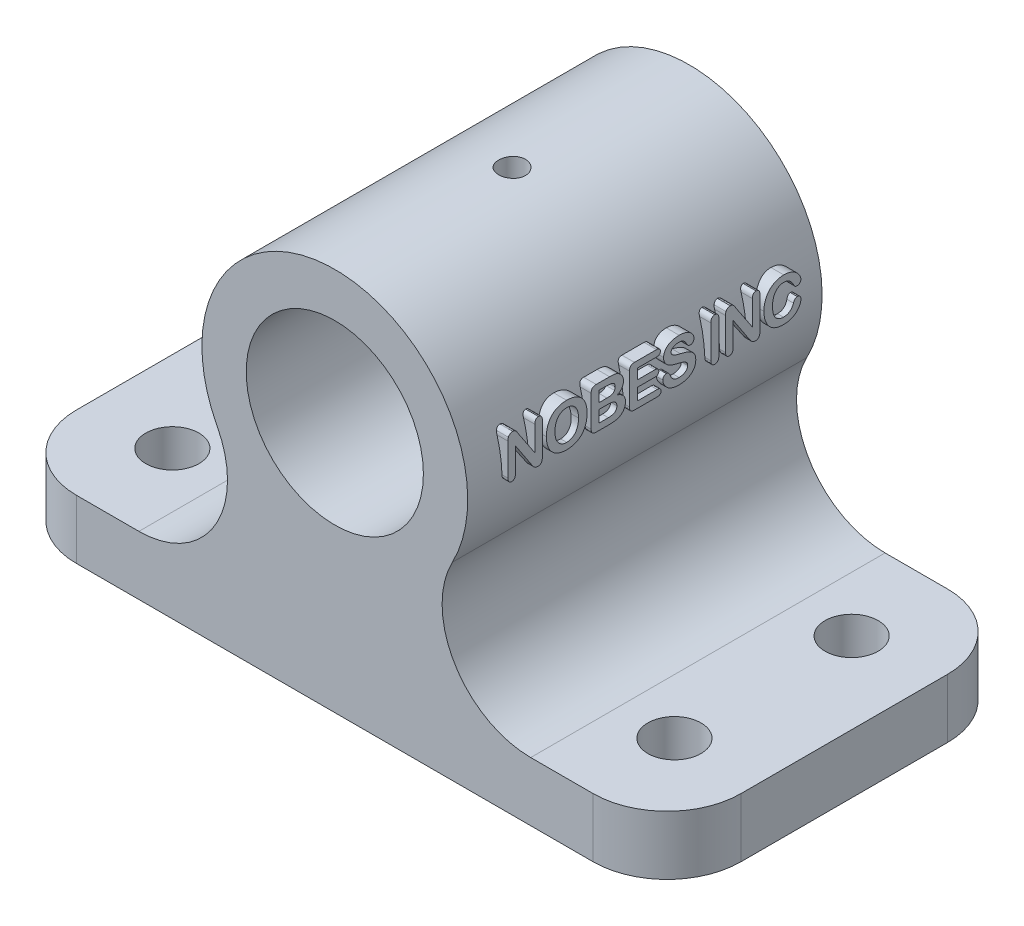
SolidWorks part; units mm, degrees
material "Malleable Cast Iron"
ref_plane "Front Plane" through (0, 0, 0) normal (0, 0, 1) x (1, 0, 0)
ref_plane "Top Plane" through (0, 0, 0) normal (0, 1, 0) x (1, 0, 0)
ref_plane "Right Plane" through (0, 0, 0) normal (1, 0, 0) x (0, 0, -1)
ref_plane "Plane1" through (0, 85, 0) normal (0, 1, 0) x (-1, 0, 0)
sketch "Sketch1" plane through (0, 0, 0) normal (0, 0, 1) x (1, 0, 0)
  line L0 (-112.5, 0) -> (112.5, 0)
  line L1 (112.5, 0) -> (112.5, 20)
  line L2 (112.5, 20) -> (66.3325, 20)
  line L6 (-66.3325, 20) -> (-112.5, 20)
  line L7 (-112.5, 20) -> (-112.5, 0)
  line L9 (0, 124.2495) -> (0, -20.5762) construction
  arc A0 (-39.7995, 64) -> (39.7995, 64) centre (0, 85) cw
  arc A1 (-39.7995, 64) -> (-66.3325, 20) centre (-66.3325, 50) cw
  arc A2 (39.7995, 64) -> (66.3325, 20) centre (66.3325, 50) ccw
  circle A3 centre (0, 85) radius 30
  point P2 (0, 0)
  dimension "D1" = 45
  dimension "D4" = 30
  dimension "D5" = 60
  dimension "D2" = 20
  dimension "D3" = 85
  dimension "D6" = 225
extrude "Main Body" add sketch "Sketch1" along normal blind 120
fillet "Fillet1" radius 25 4 edges at (112.5, 10, 120) (112.5, 10, 0) (-112.5, 10, 0) (-112.5, 10, 120)
hole_wizard "Ø18.0 (18) Diameter Hole1" positions "3DSketch1" profile "Sketch2" hole size "Ø18.0" standard "ANSI Metric" end condition through all
sketch3d "3DSketch1"
  line L0 (-66.3325, 20, 0) -> (-87.5, 20, 0) construction
  point P0 (-85, 20, 30)
  dimension "D2" = 30
  dimension "D1" = 85
sketch "Sketch2" plane through (-85, 20, 30) normal (1, 0, 0) x (0, 0, 1)
  line L0 (0, 0) -> (0, 20)
  line L1 (0, 20) -> (9, 20)
  line L2 (9, 20) -> (9, 0)
  line L5 (9, 0) -> (0, 0)
  line L11 (0, -6.35) -> (0, 107.95) construction
  dimension "Thru Hole Dia." = 18
  dimension "Thru Hole Depth" = 20
pattern_linear "LPattern1" count 2 spacing 170 along (1, 0, 0) count 2 spacing 60 along (0, 0, 1) of "Ø18.0 (18) Diameter Hole1"
ref_plane "Plane2" through (40, 0, 0) normal (1, 0, 0) x (0, 0, -1)
sketch "Sketch5" plane through (40, 0, 0) normal (1, 0, 0) x (0, 0, -1)
  line L0 (-110, 85) -> (-10, 85) construction
  line L1 (-120, 64) -> (-120, 20) construction
  line L2 (-95, 0) -> (-25, 0) construction
  text T0 "NOBES INC" font "Arial Rounded MT Bold" height in points 48
  dimension "D1" = 100
  dimension "D2" = 10
  dimension "D3" = 85
extrude "Name PLate" add sketch "Sketch5" along normal blind 7
ref_plane "Plane for Grease Nipple" through (0, 130, 0) normal (0, 1, 0) x (1, 0, 0)
hole_wizard "1/8-27 NPSM Tapped Hole1" positions "Sketch6" profile "Sketch7" tap size "1/8-27 NPSM" standard "ANSI Inch" end condition up to next
sketch "Sketch6" plane through (0, 130, 0) normal (0, 1, 0) x (1, 0, 0)
  line L0 (0, -66) -> (0, 66) construction
  line L1 (45, 0) -> (-45, 0) construction
  point P0 (0, -60)
  point P9 (0, 0)
  dimension "D1" = 60
cosmetic thread "Hole Thread2" parameters "D2"=10.0838
sketch "Sketch7" plane through (0, 130, 60) normal (1, 0, 0) x (0, 0, 1)
  line L0 (0, 0) -> (0, 15)
  line L1 (0, 15) -> (4.5466, 15)
  line L2 (4.5466, 15) -> (4.5466, 0)
  line L5 (4.5466, 0) -> (0, 0)
  line L11 (0, -6.35) -> (0, 107.95) construction
  dimension "Thru Tap Drill Dia." = 9.0932
  dimension "Thru Tap Drill Depth" = 15
equation "\"D2@3DSketch1\"=30"
